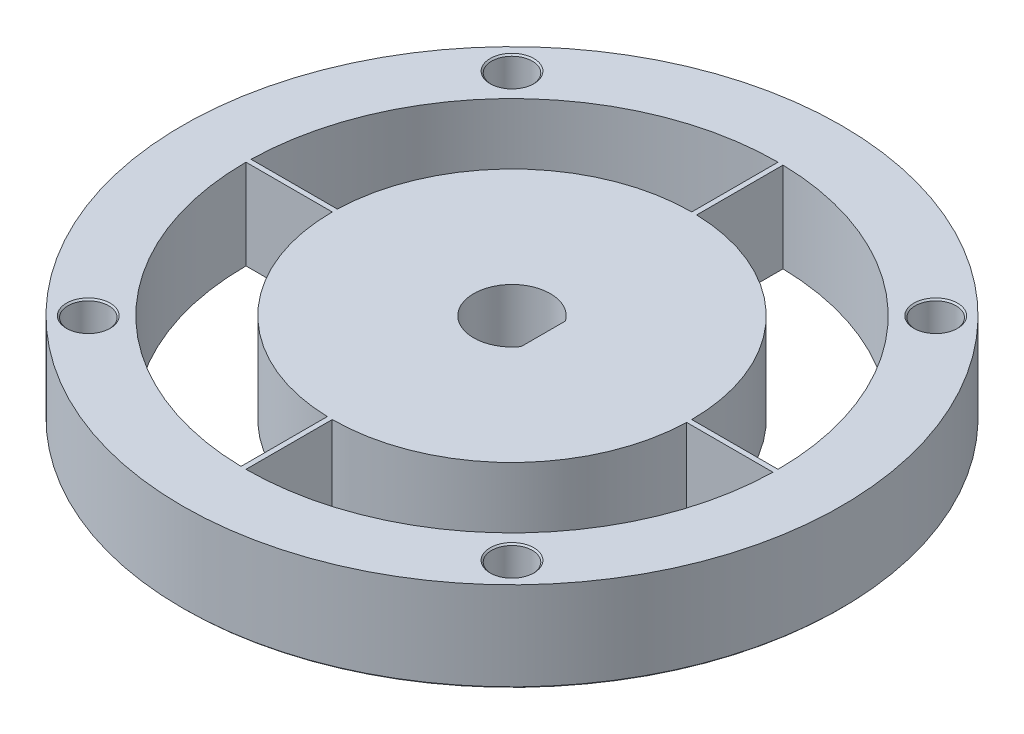
SolidWorks part; units mm, degrees
ref_plane "Front Plane" through (0, 0, 0) normal (0, 0, 1) x (1, 0, 0)
ref_plane "Top Plane" through (0, 0, 0) normal (0, 1, 0) x (1, 0, 0)
ref_plane "Right Plane" through (0, 0, 0) normal (1, 0, 0) x (0, 0, -1)
sketch "Sketch2" plane through (0, 0, 0) normal (0, 1, 0) x (1, 0, 0)
  line L0 (0, -15) -> (0, -11.9832)
  line L1 (0, -11.9832) -> (-0.175, -11.9832)
  line L2 (-15, 0) -> (-11.9832, 0)
  line L3 (0, -11.9832) -> (-0.42, -11.9832)
  line L4 (-0.42, -11.9832) -> (-0.42, -14.9941)
  line L5 (-11.9832, 0.42) -> (-14.9941, 0.42)
  line L6 (-11.9832, 0) -> (-11.9832, 0.42)
  line L7 (0, 15) -> (0, 11.9832)
  line L8 (0.42, 11.9832) -> (0.42, 14.9941)
  line L9 (0, 11.9832) -> (0.42, 11.9832)
  line L10 (15, 0) -> (11.9832, 0)
  line L11 (11.9832, -0.42) -> (14.9941, -0.42)
  line L12 (11.9832, 0) -> (11.9832, -0.42)
  arc A0 (0, -15) -> (14.9941, -0.42) centre (0, 0) ccw
  arc A1 (-0.42, -14.9941) -> (0, -15) centre (0, 0) ccw construction
  arc A2 (-15, 0) -> (-0.42, -14.9941) centre (0, 0) ccw
  arc A3 (-14.9941, 0.42) -> (-15, 0) centre (0, 0) ccw construction
  arc A4 (0, 15) -> (-14.9941, 0.42) centre (0, 0) ccw
  arc A5 (0.42, 14.9941) -> (0, 15) centre (0, 0) ccw construction
  arc A6 (15, 0) -> (0.42, 14.9941) centre (0, 0) ccw
  arc A7 (14.9941, -0.42) -> (15, 0) centre (0, 0) ccw construction
  circle A8 centre (0, 0) radius 22.1975
  circle A9 centre (0, 0) radius 27.5
  point P22 (0, 0)
  dimension "D1" = 30
  dimension "D3" = 55
  dimension "D2" = 4
  dimension "D4" = 0.42
extrude "Boss-Extrude3" add sketch "Sketch2" along normal blind 7.5 contours L0 A0 L11 L12 L10 A6 L8 L9 L7 A4 L5 L6 L2 A2 L4 L3 | A8 | A9
sketch "Sketch4" plane through (0, 7.5, 0) normal (0, 1, 0) x (1, 0, 0)
  circle A0 centre (0, 0) radius 27.5
  dimension "D1" = 55
sketch "Sketch5" plane through (0, 0, 0) normal (0, -1, 0) x (1, 0, 0)
  line L0 (0, -11.9832) -> (0, -25.4832)
  line L1 (0.42, -11.9832) -> (0.42, -25.4832)
  line L2 (0, -25.4832) -> (0.42, -25.4832)
  line L3 (-25.4832, 0) -> (-25.4832, -0.42)
  line L4 (-11.9832, -0.42) -> (-25.4832, -0.42)
  line L5 (-11.9832, 0) -> (-25.4832, 0)
  line L6 (0, 25.4832) -> (-0.42, 25.4832)
  line L7 (-0.42, 11.9832) -> (-0.42, 25.4832)
  line L8 (0, 11.9832) -> (0, 25.4832)
  line L9 (25.4832, 0) -> (25.4832, 0.42)
  line L10 (11.9832, 0.42) -> (25.4832, 0.42)
  line L11 (11.9832, 0) -> (25.4832, 0)
  line L12 (0, -11.9832) -> (0.42, -11.9832)
  line L13 (11.9832, 0.42) -> (11.9832, 0)
  line L14 (-11.9832, 0) -> (-11.9832, -0.42)
  line L15 (-0.42, 11.9832) -> (0, 11.9832)
  circle A0 centre (-17.6777, 17.6777) radius 1.7
  circle A1 centre (17.6777, 17.6777) radius 1.7
  circle A2 centre (17.6777, -17.6777) radius 1.7
  circle A3 centre (-17.6777, -17.6777) radius 1.7
  point P22 (0, 0)
  point P28 (0, 0)
  point P36 (0, 0)
  dimension "D3" = 3.4
  dimension "D2" = 13.5
  dimension "D1" = 4
  dimension "D5" = 4
sketch "Sketch7" plane through (0, 0, 0) normal (0, -1, 0) x (1, 0, 0)
  line L0 (2.611, 1.85) -> (2.611, -1.85)
  arc A0 (2.611, 1.85) -> (2.611, -1.85) centre (0, 0) ccw
  arc A1 (2.611, -1.85) -> (2.611, 1.85) centre (0, 0) ccw construction
  dimension "D1" = 6.4
extrude "Cut-Extrude6" cut sketch "Sketch5" against normal through all contours L0 L2 L1 L12 | L5 L3 L4 L14 | A0 | L7 L6 L8 L15 | A1 | L11 L9 L10 L13 | A2 | A3
extrude "Cut-Extrude8" cut sketch "Sketch7" against normal blind 7.5 contours A0 L0
chamfer "Chamfer3" distance 0.125 angle 45 2 edges at (2.611, 0, 0) (-3.2, 0, 0)
chamfer "Chamfer4" distance 0.125 angle 45 9 edges at (0, 0, 27.5) (17.6777, 0, 15.9777) (17.6777, 0, -19.3777) (-17.6777, 0, -19.3777) (-17.6777, 0, 15.9777) (-17.6777, 7.5, 15.9777) (17.6777, 7.5, 15.9777) (17.6777, 7.5, -19.3777) (-17.6777, 7.5, -19.3777)
sketch "Sketch14" plane through (0, 0, 0) normal (0, -1, 0) x (1, 0, 0)
  line L1 (-0.42, 11.9832) -> (0, 11.9832)
  line L2 (-0.42, 11.9832) -> (-0.42, 25.4832)
  line L3 (-0.42, 25.4832) -> (0, 25.4832)
  line L4 (0, 11.9832) -> (0, 25.4832)
  line L5 (11.9832, 0.42) -> (25.4832, 0.42)
  line L6 (11.9832, 0.42) -> (11.9832, 0)
  line L7 (11.9832, 0) -> (25.4832, 0)
  line L8 (25.4832, 0.42) -> (25.4832, 0)
  line L9 (0, -11.9832) -> (0.42, -11.9832)
  line L10 (0, -11.9832) -> (0, -25.4832)
  line L11 (0, -25.4832) -> (0.42, -25.4832)
  line L12 (0.42, -11.9832) -> (0.42, -25.4832)
  line L13 (-25.4832, 0) -> (-11.9832, 0)
  line L14 (-25.4832, 0) -> (-25.4832, -0.42)
  line L15 (-25.4832, -0.42) -> (-11.9832, -0.42)
  line L16 (-11.9832, 0) -> (-11.9832, -0.42)
extrude "Boss-Extrude5" add sketch "Sketch14" against normal blind 7.5
ref_axis "Axis1" through (0, 7.5, 0) along (0, -1, 0)
